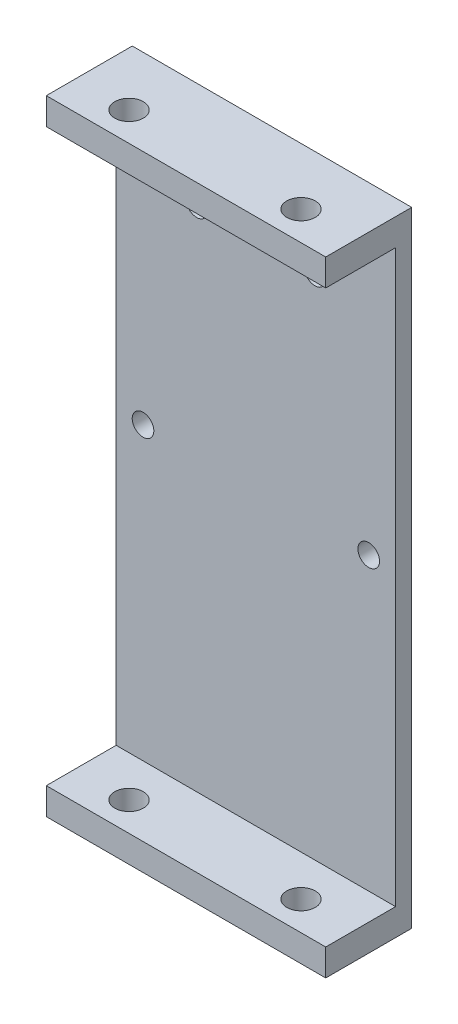
SolidWorks part; units mm, degrees
ref_plane "Front Plane" through (0, 0, 0) normal (0, 0, 1) x (1, 0, 0)
ref_plane "Top Plane" through (0, 0, 0) normal (0, 1, 0) x (1, 0, 0)
ref_plane "Right Plane" through (0, 0, 0) normal (1, 0, 0) x (0, 0, -1)
sketch "Sketch1" plane through (0, 0, 0) normal (0, 0, 1) x (1, 0, 0)
  line L0 (66.04, 81.2371) -> (66.04, 68.7911) construction
  line L1 (0, 0) -> (66.04, 0)
  line L2 (0, 0) -> (0, 147.574)
  line L3 (0, 147.574) -> (66.04, 147.574)
  line L4 (66.04, 0) -> (66.04, 147.574)
  dimension "D2" = 147.574
extrude "Boss-Extrude1" add sketch "Sketch1" along normal blind 3.81
sketch "Sketch3" plane through (0, 0, 3.81) normal (0, 0, 1) x (1, 0, 0)
  line L0 (66.04, 0) -> (66.04, 147.574) construction
  line L1 (0, 147.574) -> (66.04, 147.574)
  line L2 (0, 147.574) -> (0, 141.224)
  line L3 (0, 141.224) -> (66.04, 141.224)
  line L4 (66.04, 147.574) -> (66.04, 141.224)
  line L6 (0, 0) -> (66.04, 0)
  line L7 (0, 0) -> (0, 6.35)
  line L8 (0, 6.35) -> (66.04, 6.35)
  line L9 (66.04, 0) -> (66.04, 6.35)
  dimension "D1" = 6.35
  dimension "D2" = 6.35
extrude "Boss-Extrude2" add sketch "Sketch3" along normal blind 16.51
sketch "Sketch4" plane through (0, 0, 0) normal (0, -1, 0) x (1, 0, 0)
  line L0 (0, 20.32) -> (66.04, 20.32) construction
  line L3 (0, 20.32) -> (0, 0) construction
  circle A0 centre (12.7, 13.462) radius 3.3782
  circle A5 centre (53.34, 13.462) radius 3.3782
  dimension "D2" = 6.7564
  dimension "D3" = 6.7564
  dimension "D4" = 6.858
  dimension "D6" = 6.858
  dimension "D1" = 40.64
  dimension "D5" = 12.7
extrude "Cut-Extrude1" cut sketch "Sketch4" against normal through all
sketch "Sketch5" plane through (0, 0, 3.81) normal (0, 0, 1) x (1, 0, 0)
  circle A0 centre (46.99, 126.4491) radius 2.5527 construction
  circle A1 centre (19.05, 126.4491) radius 2.5527 construction
  circle A2 centre (6.35, 75.1411) radius 2.5527 construction
  circle A3 centre (59.69, 75.1411) radius 2.5527 construction
  circle A4 centre (46.99, 126.4491) radius 2.5527
  circle A5 centre (19.05, 126.4491) radius 2.5527
  circle A6 centre (6.35, 75.1411) radius 2.5527
  circle A7 centre (59.69, 75.1411) radius 2.5527
extrude "Cut-Extrude2" cut sketch "Sketch5" against normal up to surface (3.81 mm away) up to face at (33.02, 73.787, 0)
